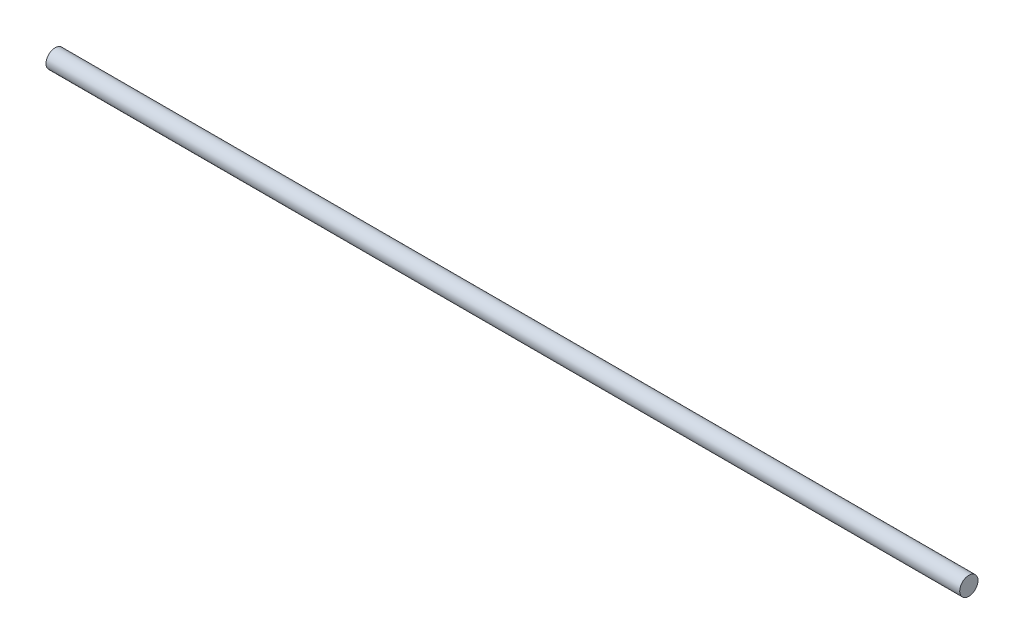
SolidWorks part; units mm, degrees
ref_plane "Front Plane" through (0, 0, 0) normal (0, 0, 1) x (1, 0, 0)
ref_plane "Top Plane" through (0, 0, 0) normal (0, 1, 0) x (1, 0, 0)
ref_plane "Right Plane" through (0, 0, 0) normal (1, 0, 0) x (0, 0, -1)
sketch "Sketch3" plane through (0, 0, 0) normal (1, 0, 0) x (0, 0, -1)
  circle A0 centre (0, 0) radius 4
extrude "Boss-Extrude1" add sketch "Sketch3" along normal blind 400
